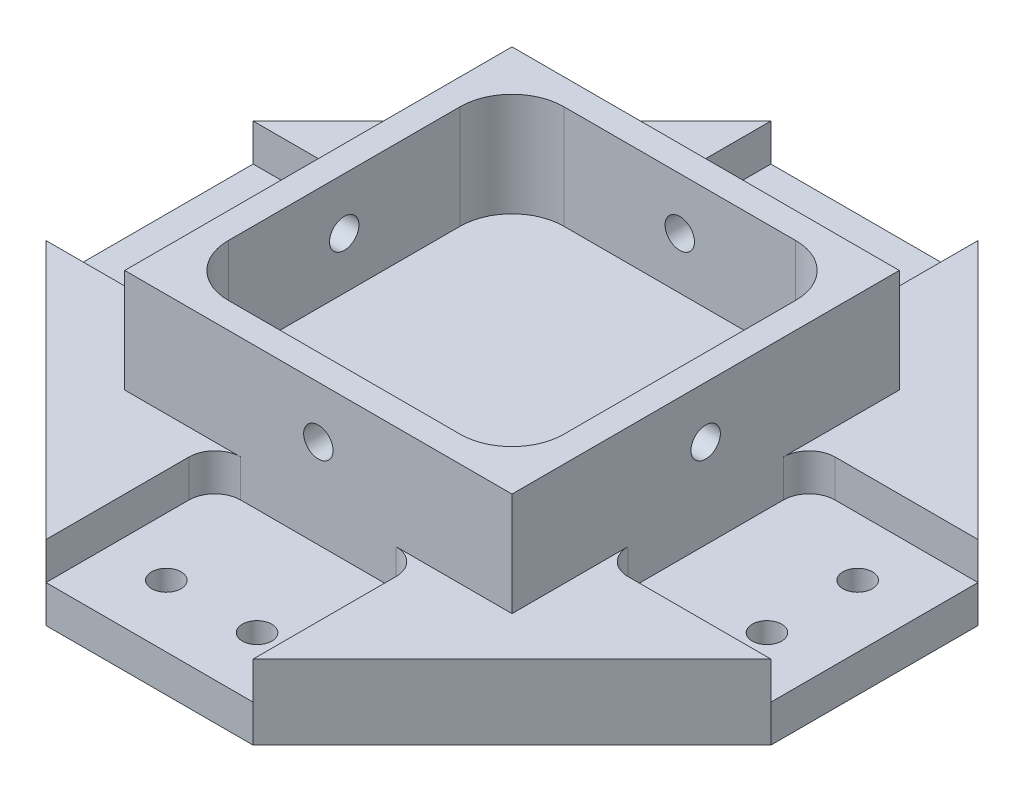
SolidWorks part; units mm, degrees
material "6061 Alloy"
ref_plane "Front Plane" through (0, 0, 0) normal (0, 0, 1) x (1, 0, 0)
ref_plane "Top Plane" through (0, 0, 0) normal (0, 1, 0) x (1, 0, 0)
ref_plane "Right Plane" through (0, 0, 0) normal (1, 0, 0) x (0, 0, -1)
sketch "Sketch1" plane through (0, 0, 0) normal (0, 1, 0) x (1, 0, 0)
  line L1 (0, 0) -> (88.9, 0)
  line L2 (0, 0) -> (0, 88.9)
  line L3 (0, 88.9) -> (88.9, 88.9)
  line L4 (88.9, 0) -> (88.9, 88.9)
  dimension "D1" = 88.9
  dimension "D2" = 88.9
extrude "Boss-Extrude1" add sketch "Sketch1" along normal blind 9.144
sketch "Sketch2" plane through (0, 9.144, 0) normal (0, 1, 0) x (1, 0, 0)
  line L0 (88.9, 88.9) -> (0, 88.9) construction
  line L1 (31.75, 88.9) -> (57.15, 88.9)
  line L2 (31.75, 88.9) -> (31.75, 67.31)
  line L3 (31.75, 67.31) -> (57.15, 67.31)
  line L4 (57.15, 88.9) -> (57.15, 67.31)
  line L5 (0, 88.9) -> (0, 0) construction
  line L6 (0, 57.15) -> (21.59, 57.15)
  line L7 (0, 57.15) -> (0, 31.75)
  line L8 (0, 31.75) -> (21.59, 31.75)
  line L9 (21.59, 57.15) -> (21.59, 31.75)
  line L10 (0, 0) -> (88.9, 0) construction
  line L11 (31.75, 0) -> (57.15, 0)
  line L12 (31.75, 0) -> (31.75, 21.59)
  line L13 (31.75, 21.59) -> (57.15, 21.59)
  line L14 (57.15, 0) -> (57.15, 21.59)
  line L15 (88.9, 0) -> (88.9, 88.9) construction
  line L16 (88.9, 57.15) -> (67.31, 57.15)
  line L17 (88.9, 57.15) -> (88.9, 31.75)
  line L18 (88.9, 31.75) -> (67.31, 31.75)
  line L19 (67.31, 57.15) -> (67.31, 31.75)
  dimension "D1" = 31.75
  dimension "D2" = 25.4
  dimension "D3" = 25.4
  dimension "D4" = 31.75
  dimension "D5" = 25.4
  dimension "D6" = 31.75
  dimension "D7" = 25.4
  dimension "D8" = 31.75
  dimension "D9" = 21.59
  dimension "D10" = 21.59
  dimension "D11" = 21.59
  dimension "D12" = 21.59
extrude "Cut-Extrude1" cut sketch "Sketch2" against normal blind 4.572
sketch "Sketch3" plane through (0, 9.144, 0) normal (0, 1, 0) x (1, 0, 0)
  line L0 (31.75, 88.9) -> (0, 88.9) construction
  line L1 (20.6375, 68.2625) -> (68.2625, 68.2625)
  line L2 (20.6375, 68.2625) -> (20.6375, 20.6375)
  line L3 (20.6375, 20.6375) -> (68.2625, 20.6375)
  line L4 (68.2625, 68.2625) -> (68.2625, 20.6375)
  line L5 (0, 31.75) -> (0, 0) construction
  line L6 (88.9, 31.75) -> (88.9, 57.15) construction
  line L7 (57.15, 88.9) -> (31.75, 88.9) construction
  line L8 (0, 57.15) -> (0, 31.75) construction
  line L9 (31.75, 0) -> (57.15, 0) construction
  circle A0 centre (28.194, 44.45) radius 2.4
  circle A1 centre (44.45, 60.706) radius 2.4
  circle A2 centre (60.706, 44.45) radius 2.4
  circle A3 centre (44.45, 28.194) radius 2.4
  dimension "D5" = 4.8
  dimension "D6" = 4.8
  dimension "D7" = 4.8
  dimension "D8" = 4.8
  dimension "D1" = 47.625
  dimension "D2" = 47.625
  dimension "D3" = 20.6375
  dimension "D4" = 20.6375
  dimension "D9" = 28.194
  dimension "D10" = 28.194
  dimension "D11" = 28.194
  dimension "D12" = 28.194
  dimension "D13" = 23.8125
  dimension "D14" = 23.8125
  dimension "D15" = 23.8125
  dimension "D16" = 23.8125
extrude "Cut-Extrude2" [suppressed] cut sketch "Sketch3" against normal through all contours A2 | A1 | A0 | A3
sketch "Sketch4" plane through (0, 4.572, 0) normal (0, 1, 0) x (1, 0, 0)
  line L0 (0, 57.15) -> (0, 31.75) construction
  line L1 (57.15, 88.9) -> (31.75, 88.9) construction
  line L2 (88.9, 31.75) -> (88.9, 57.15) construction
  line L3 (31.75, 0) -> (57.15, 0) construction
  line L4 (0, 31.75) -> (21.59, 31.75) construction
  line L5 (31.75, 21.59) -> (31.75, 0) construction
  line L6 (67.31, 31.75) -> (88.9, 31.75) construction
  line L7 (57.15, 67.31) -> (57.15, 88.9) construction
  circle A0 centre (81.28, 50.0126) radius 1.8034
  circle A1 centre (81.28, 38.8874) radius 1.8034
  circle A2 centre (50.0126, 81.28) radius 1.8034
  circle A3 centre (38.8874, 81.28) radius 1.8034
  circle A4 centre (7.62, 50.0126) radius 1.8034
  circle A5 centre (7.62, 38.8874) radius 1.8034
  circle A6 centre (38.8874, 7.62) radius 1.8034
  circle A7 centre (50.0126, 7.62) radius 1.8034
  dimension "D1" = 3.6068
  dimension "D2" = 3.6068
  dimension "D3" = 3.6068
  dimension "D4" = 3.6068
  dimension "D5" = 3.6068
  dimension "D6" = 3.6068
  dimension "D7" = 3.6068
  dimension "D8" = 3.6068
  dimension "D9" = 7.62
  dimension "D10" = 7.62
  dimension "D11" = 7.62
  dimension "D12" = 7.62
  dimension "D13" = 7.62
  dimension "D14" = 7.62
  dimension ".313" = 7.62
  dimension "D16" = 7.62
  dimension "D17" = 11.1252
  dimension "D18" = 7.1374
  dimension "D19" = 7.1374
  dimension "D20" = 11.1252
  dimension "D21" = 7.1374
  dimension "D22" = 11.1252
  dimension "D23" = 7.1374
  dimension "D24" = 11.1252
extrude "Cut-Extrude3" cut sketch "Sketch4" against normal through all
sketch "Sketch5" plane through (0, 9.144, 0) normal (0, 1, 0) x (1, 0, 0)
  line L0 (88.9, 88.9) -> (57.15, 88.9) construction
  line L1 (88.9, 31.75) -> (88.9, 57.15) construction
  circle A0 centre (44.45, 44.45) radius 6.35
  dimension "D1" = 12.7
  dimension "D2" = 44.45
  dimension "D3" = 44.45
extrude "Cut-Extrude4" [suppressed] cut sketch "Sketch5" against normal through all
sketch "Sketch6" plane through (0, 9.144, 0) normal (0, 1, 0) x (1, 0, 0)
  line L0 (88.9, 31.75) -> (57.15, 0)
  line L1 (57.15, 0) -> (88.9, 0)
  line L2 (88.9, 0) -> (88.9, 31.75)
extrude "Cut-Extrude5" cut sketch "Sketch6" against normal through all
sketch "Sketch7" plane through (0, 9.144, 0) normal (0, 1, 0) x (1, 0, 0)
  line L0 (0, 88.9) -> (0, 57.15) construction
  line L1 (20.701, 68.199) -> (68.199, 68.199)
  line L2 (20.701, 68.199) -> (20.701, 20.701)
  line L3 (20.701, 20.701) -> (68.199, 20.701)
  line L4 (68.199, 68.199) -> (68.199, 20.701)
  line L5 (0, 0) -> (31.75, 0) construction
  line L7 (23.876, 23.876) -> (65.024, 23.876)
  line L8 (23.876, 23.876) -> (23.876, 65.024)
  line L9 (23.876, 65.024) -> (65.024, 65.024)
  line L10 (65.024, 23.876) -> (65.024, 65.024)
  dimension "D1" = 47.498
  dimension "D2" = 47.498
  dimension "D3" = 20.701
  dimension "D4" = 20.701
  dimension "D5" = 3.175
  dimension "D6" = 3.175
  dimension "D7" = 3.175
  dimension "D8" = 3.175
extrude "Boss-Extrude2" add sketch "Sketch7" along normal blind 12.7 and the other way up to next (4.572 mm away)
fillet "Fillet9" radius 6.35 1 edges at (65.024, 15.494, -23.876)
fillet "Fillet10" radius 6.35 1 edges at (23.876, 15.494, -23.876)
fillet "Fillet11" radius 6.35 1 edges at (65.024, 15.494, -65.024)
fillet "Fillet12" radius 6.35 1 edges at (23.876, 15.494, -65.024)
fillet "Fillet15" radius 3.175 1 edges at (20.701, 6.858, -57.15)
fillet "Fillet16" radius 3.175 1 edges at (31.75, 6.858, -20.701)
fillet "Fillet17" radius 3.175 1 edges at (57.15, 6.858, -20.701)
fillet "Fillet18" radius 3.175 1 edges at (68.199, 6.858, -57.15)
fillet "Fillet19" radius 3.175 1 edges at (68.199, 6.858, -31.75)
fillet "Fillet20" radius 3.175 1 edges at (31.75, 6.858, -68.199)
fillet "Fillet21" radius 3.175 1 edges at (57.15, 6.858, -68.199)
fillet "Fillet22" radius 3.175 1 edges at (20.701, 6.858, -31.75)
sketch "Sketch9" plane through (0, 0, -68.199) normal (0, 0, -1) x (-1, 0, 0)
  line L0 (-68.199, 21.844) -> (-68.199, 9.144) construction
  line L1 (-68.199, 21.844) -> (-20.701, 21.844) construction
  circle A0 centre (-44.45, 15.494) radius 1.8034
  dimension "D1" = 3.6068
  dimension "D2" = 23.749
  dimension "D3" = 6.35
extrude "Cut-Extrude6" cut sketch "Sketch9" against normal through all
sketch "Sketch10" plane through (68.199, 0, 0) normal (1, 0, 0) x (0, 0, -1)
  line L0 (20.701, 21.844) -> (68.199, 21.844) construction
  line L1 (20.701, 21.844) -> (20.701, 9.144) construction
  circle A0 centre (44.45, 15.494) radius 1.8034
  dimension "D1" = 3.6068
  dimension "D2" = 6.35
  dimension "D3" = 23.749
extrude "Cut-Extrude7" cut sketch "Sketch10" against normal through all
sketch "Sketch12" plane through (0, 9.144, 0) normal (0, 1, 0) x (1, 0, 0)
  line L0 (0, 31.75) -> (31.75, 0)
  line L1 (31.75, 0) -> (0, 0)
  line L2 (0, 0) -> (0, 31.75)
  line L3 (57.15, 88.9) -> (88.9, 57.15)
  line L4 (88.9, 57.15) -> (88.9, 88.9)
  line L5 (88.9, 88.9) -> (57.15, 88.9)
  line L6 (0, 57.15) -> (31.75, 88.9)
  line L7 (31.75, 88.9) -> (0, 88.9)
  line L8 (0, 88.9) -> (0, 57.15)
sketch "Sketch14" plane through (0, 0, 0) normal (0, -1, 0) x (1, 0, 0)
  line L1 (0, -88.9) -> (0, 0) construction
  line L3 (0, 0) -> (57.15, 0) construction
  circle A0 centre (27.9855, -27.906) radius 2.5797
  circle A1 centre (59.4164, -59.3369) radius 2.5797
  dimension "D1" = 44.45
  dimension "D2" = 5.1594
  dimension "D3" = 5.1594
  dimension "D4" = 27.9855
  dimension "D6" = 27.906
extrude "Cut-Extrude9" cut sketch "Sketch14" against normal through all
extrude "Cut-Extrude10" cut sketch "Sketch12" against normal through all
equation "\"hinge_hole\"= 0.142in"
equation "\"D1@Sketch4\"=\"hinge_hole\""
equation "\"D2@Sketch4\"=\"hinge_hole\""
equation "\"D3@Sketch4\"=\"hinge_hole\""
equation "\"D4@Sketch4\"=\"hinge_hole\""
equation "\"D5@Sketch4\"=\"hinge_hole\""
equation "\"D6@Sketch4\"=\"hinge_hole\""
equation "\"D7@Sketch4\"=\"hinge_hole\""
equation "\"D8@Sketch4\"=\"hinge_hole\""
equation "\"hinge_hole_dist\"= 0.297 + 0.25"
equation "\".313@Sketch4\"=.3"
equation "\"hinge_hole_sep\"=0.438"
equation "\"hinge_hole_from_wall\"= ( 1 - \"hinge_hole_sep\" ) / 2"
equation "\"D17@Sketch4\"=\"hinge_hole_sep\""
equation "\"D18@Sketch4\"=\"hinge_hole_from_wall\""
equation "\"D19@Sketch4\"=\"hinge_hole_from_wall\""
equation "\"D20@Sketch4\"=\"hinge_hole_sep\""
equation "\"D21@Sketch4\"=\"hinge_hole_from_wall\""
equation "\"D22@Sketch4\"=\"hinge_hole_sep\""
equation "\"D23@Sketch4\"=\"hinge_hole_from_wall\""
equation "\"D24@Sketch4\"=\"hinge_hole_sep\""
equation "\"D9@Sketch2\"=\"hinge_hole_dist\" + (0.6-0.297)"
equation "\"D12@Sketch2\"=\"hinge_hole_dist\" + (0.6-0.297)"
equation "\"D11@Sketch2\"=\"hinge_hole_dist\" + (0.6-0.297)"
equation "\"D10@Sketch2\"=\"hinge_hole_dist\" + (0.6-0.297)"
